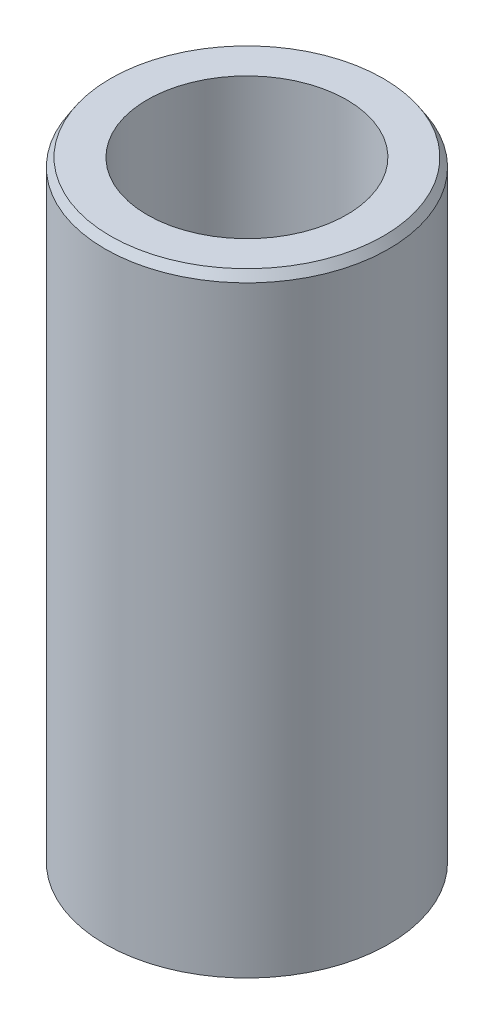
SolidWorks part; units mm, degrees
ref_plane "Front Plane" through (0, 0, 0) normal (0, 0, 1) x (1, 0, 0)
ref_plane "Top Plane" through (0, 0, 0) normal (0, 1, 0) x (1, 0, 0)
ref_plane "Right Plane" through (0, 0, 0) normal (1, 0, 0) x (0, 0, -1)
sketch "Sketch1" plane through (0, 0, 0) normal (0, 1, 0) x (1, 0, 0)
  circle A0 centre (0, 0) radius 40
  dimension "SHAFT_OD" = 80
extrude "Boss-Extrude1" add sketch "Sketch1" along normal blind 173.6658
sketch "Sketch2" plane through (0, 0, 0) normal (0, 1, 0) x (1, 0, 0)
  circle A0 centre (0, 0) radius 28.1167
  dimension "BORE_D" = 56.2334
extrude "Cut-Extrude1" cut sketch "Sketch2" along normal through all
chamfer "Chamfer1" distance 2.3911 angle 32.535 2 edges at (0, 173.6658, 40) (0, 0, 40) first distance on face at (0, 173.6658, 40) first distance on face at (0, 0, 28.1167)
